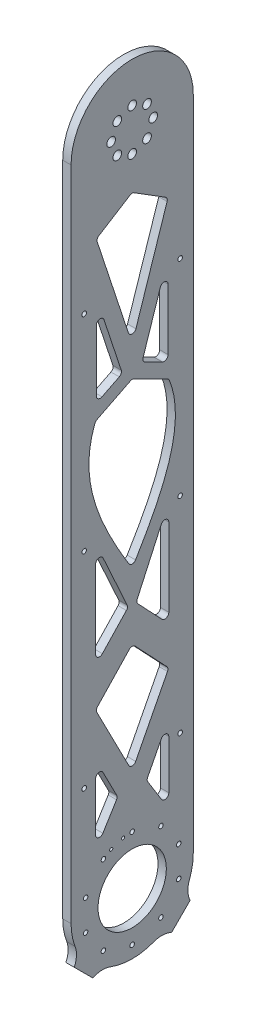
SolidWorks part; units mm, degrees
note: '?' marks a value the reader was unsure of.
material "6061 Alloy"
ref_plane "Front Plane" through (0, 0, 0) normal (0, 0, 1) x (1, 0, 0)
ref_plane "Top Plane" through (0, 0, 0) normal (0, 1, 0) x (1, 0, 0)
ref_plane "Right Plane" through (0, 0, 0) normal (1, 0, 0) x (0, 0, -1)
sketch "Sketch1" plane through (0, 0, 0) normal (1, 0, 0) x (0, -1, 0)
  line L0 (0, 0) -> (500, 0) construction
  line L1 (0, 46.5) -> (500, 46.5)
  line L2 (0, -46.5) -> (500, -46.5)
  arc A0 (0, 46.5) -> (0, -46.5) centre (0, 0) ccw
  arc A1 (500, -46.5) -> (500, 46.5) centre (500, 0) ccw
  circle A2 centre (0, 0) radius 16 construction
  circle A3 centre (-16, 0) radius 3.3
  circle A4 centre (-11.3137, 11.3137) radius 3.3
  circle A5 centre (0, 16) radius 3.3
  circle A6 centre (11.3137, 11.3137) radius 3.3
  circle A7 centre (16, 0) radius 3.3
  circle A8 centre (11.3137, -11.3137) radius 3.3
  circle A27 centre (500, 0) radius 37.25 construction
  circle A28 centre (537.25, 0) radius 1.7
  circle A29 centre (500, 0) radius 37.25 construction
  circle A30 centre (537.25, 0) radius 1.7
  circle A31 centre (530.1359, -21.895) radius 1.7
  circle A32 centre (511.5109, -35.4269) radius 1.7
  circle A33 centre (488.4891, -35.4269) radius 1.7
  circle A34 centre (469.8641, -21.895) radius 1.7
  circle A35 centre (462.75, 0) radius 1.7
  circle A36 centre (469.8641, 21.895) radius 1.7
  circle A37 centre (488.4891, 35.4269) radius 1.7
  circle A38 centre (511.5109, 35.4269) radius 1.7
  circle A39 centre (530.1359, 21.895) radius 1.7
  circle A40 centre (500, 0) radius 26
  circle A41 centre (0, -16) radius 3.3
  circle A42 centre (-11.3137, -11.3137) radius 3.3
  point P3 (250, 0)
  point P25 (0, 0)
  point P52 (500, 0)
  point P61 (500, 0)
  dimension "D3" = 32
  dimension "D4" = 6.6
  dimension "D2" = 74.5
  dimension "D7" = 3.4
  dimension "D8" = 3.4
  dimension "D10" = 52
  dimension "D6" = 46.5
  dimension "D1" = 500
  dimension "D5" = 8
  dimension "D9" = 10
extrude "Boss-Extrude1" add sketch "Sketch1" along normal blind 6.35 contours L2 A1 L1 A0 A40 A39 A38 A37 A36 A35 A34 A33 A32 A31 A28 A8 A7 A6 A5 A4 A3
ref_axis "Axis1" through (6.35, -500, 0) along (-1, 0, 0)?
sketch "Sketch3" plane through (6.35, 0, 0) normal (1, 0, 0) x (0, 0, -1)
  line L0 (0, -500) -> (0, 0) construction
  line L1 (0, -422.848) -> (27.8582, -368.6328)
  line L2 (0, -422.848) -> (-27.8582, -368.6328)
  line L3 (-27.8582, -368.6328) -> (0, -339.1393)
  line L4 (0, -339.1393) -> (27.8582, -368.6328)
  line L5 (0, -41.3687) -> (-27.3129, -58.4352)
  line L6 (-27.3129, -58.4352) -> (0, -141.249)
  line L7 (0, -141.249) -> (27.3129, -58.4352)
  line L8 (27.3129, -58.4352) -> (0, -41.3687)
  line L9 (3, -313.1891) -> (27.8582, -339.5065)
  line L10 (27.8582, -339.5065) -> (27.8582, -258.646)
  line L11 (27.8582, -258.646) -> (3, -313.1891)
  line L12 (-27.8582, -339.5065) -> (-27.8582, -258.646)
  line L13 (-3, -313.1891) -> (-27.8582, -339.5065)
  line L14 (-27.8582, -258.646) -> (-3, -313.1891)
  line L15 (-27.8582, -401.4529) -> (-11, -434.2608)
  line L16 (-11, -434.2608) -> (-27.8582, -461.4818)
  line L17 (-27.8582, -461.4818) -> (-27.8582, -401.4529)
  line L18 (11, -434.2608) -> (27.8582, -461.4818)
  line L19 (27.8582, -401.4529) -> (11, -434.2608)
  line L20 (27.8582, -461.4818) -> (27.8582, -401.4529)
  line L21 (0, -164.2489) -> (-27.8582, -178.2005)
  line L22 (0, -164.2489) -> (27.8582, -178.2005)
  line L23 (7.5, -156.821) -> (27.3129, -96.7475)
  line L24 (27.3129, -96.7475) -> (27.3129, -166.7434)
  line L25 (27.3129, -166.7434) -> (7.5, -156.821)
  line L26 (-27.3129, -96.7475) -> (-27.3129, -166.7434)
  line L27 (-7.5, -156.821) -> (-27.3129, -96.7475)
  line L28 (-27.3129, -166.7434) -> (-7.5, -156.821)
  spline S0 degree 3 poles (-27.8582, -178.2005) (-43.7791, -216.0933) (-18.6166, -258.2761) (0, -289.085) knots 0 0 0 0 1 1 1 1
  spline S1 degree 3 poles (27.8582, -178.2005) (43.7791, -216.0933) (18.6166, -258.2761) (0, -289.085) knots 0 0 0 0 1 1 1 1
  dimension "D1" = 15
  dimension "D2" = 20
  dimension "D3" = 12
  dimension "D4" = 10
  dimension "D5" = 6
  dimension "D6" = 15
  dimension "D7" = 22
extrude "Cut-Extrude1" cut sketch "Sketch3" against normal through all
fillet "Fillet1" radius 3 30 edges at (3.175, -58.4352, -27.3129) (3.175, -41.3687, 0) (3.175, -58.4352, 27.3129) (3.175, -141.249, 0) (3.175, -289.085, 0) (3.175, -164.2489, 0) (3.175, -401.4529, 27.8582) (3.175, -434.2608, 11) (3.175, -461.4818, 27.8582) (3.175, -461.4818, -27.8582) (3.175, -434.2608, -11) (3.175, -401.4529, -27.8582) (3.175, -368.6328, -27.8582) (3.175, -339.1393, 0) (3.175, -368.6328, 27.8582) (3.175, -422.848, 0) (3.175, -313.1891, 3) (3.175, -339.5065, 27.8582) (3.175, -258.646, 27.8582) (3.175, -178.2005, -27.8582) (3.175, -178.2005, 27.8582) (3.175, -339.5065, -27.8582) (3.175, -313.1891, -3) (3.175, -258.646, -27.8582) (3.175, -96.7475, 27.3129) (3.175, -166.7434, 27.3129) (3.175, -156.821, 7.5) (3.175, -166.7434, -27.3129) (3.175, -156.821, -7.5) (3.175, -96.7475, -27.3129)
sketch "Sketch4" plane through (6.35, 0, 0) normal (1, 0, 0) x (0, 0, -1)
  line L0 (0, 46.5) -> (-113.1579, 46.5) construction
  line L1 (-46.5, 0) -> (-46.5, -500) construction
  line L2 (-46.5, -100) -> (46.5, -100) construction
  line L3 (46.5, 0) -> (46.5, -500) construction
  line L4 (-46.5, -106.35) -> (46.5, -106.35) construction
  line L5 (-36.5, -100) -> (-36.5, -106.35) construction
  line L6 (0, 0) -> (0, -106.35) construction
  line L7 (0, -106.35) -> (0, -256.35) construction
  line L8 (0, -256.35) -> (46.5, -256.35) construction
  line L9 (46.5, -262.7) -> (-46.5, -262.7) construction
  line L10 (0, -181.35) -> (46.5, -181.35) construction
  line L11 (0, -262.7) -> (0, -412.7) construction
  line L12 (0, -412.7) -> (46.5, -412.7) construction
  line L13 (0, -337.7) -> (46.5, -337.7) construction
  arc A1 (46.5, 0) -> (-46.5, 0) centre (0, 0) ccw construction
  circle A2 centre (-36.5, -103.175) radius 1.75
  circle A3 centre (36.5, -103.175) radius 1.75
  circle A4 centre (-36.5, -259.525) radius 1.75
  circle A5 centre (36.5, -259.525) radius 1.75
  circle A6 centre (-36.5, -415.875) radius 1.75
  circle A7 centre (36.5, -415.875) radius 1.75
  point P17 (-36.5, -103.175)
  dimension "D1" = 3.5
  dimension "D2" = 6.35
  dimension "D3" = 10
  dimension "D4" = 146.5
  dimension "D5" = 150
  dimension "D6" = 6.35
  dimension "D7" = 81.35
  dimension "D8" = 150
  dimension "D9" = 81.35
extrude "Cut-Extrude2" cut sketch "Sketch4" against normal through all
sketch "Sketch5" plane through (6.35, 0, 0) normal (1, 0, 0) x (0, 0, -1)
  line L0 (-6.9161, -463.3431) -> (-15.9511, -466.2787) construction
  line L1 (-7.2252, -475.0096) -> (7.4545, -470.2399) construction
  line L2 (-21.895, -469.8641) -> (0, -462.75) construction
  line L3 (-10.9475, -466.3071) -> (0, -500) construction
  circle A0 centre (-6.9161, -463.3431) radius 1.2
  circle A1 centre (-15.9511, -466.2787) radius 1.2
  circle A2 centre (0, -500) radius 26 construction
  circle A3 centre (0, -500) radius 26 construction
  circle A4 centre (0, -462.75) radius 1.7 construction
  circle A5 centre (-21.895, -469.8641) radius 1.7 construction
  circle A6 centre (0, -462.75) radius 1.7 construction
  circle A7 centre (-21.895, -469.8641) radius 1.7 construction
  point P16 (-11.4336, -464.8109)
  dimension "D1" = 2.4
  dimension "D2" = 9.5
  dimension "D3" = 11
extrude "Cut-Extrude4" cut sketch "Sketch5" against normal through all
sketch "Sketch6" plane through (6.35, 0, 0) normal (1, 0, 0) x (0, 0, -1)
  line L2 (-23.6842, -540.0163) -> (-29.9682, -544.1104) construction
  line L3 (-44.1104, -529.9682) -> (-29.9682, -544.1104)
  line L4 (0, -500) -> (0, -546.5) construction
  line L5 (-37.0393, -537.0393) -> (0, -500) construction
  line L6 (-44.1104, -529.9682) -> (-40.0163, -523.6842) construction
  arc A0 (-46.5, -500) -> (46.5, -500) centre (0, -500) ccw construction
  arc A1 (-29.9682, -544.1104) -> (-16.4747, -543.4837) centre (-22.4977, -559.381) cw
  arc A4 (-44.1104, -529.9682) -> (-43.4837, -516.4747) centre (-59.381, -522.4977) ccw
  arc A5 (-16.4747, -543.4837) -> (-43.4837, -516.4747) centre (0, -500) cw
  dimension "D2" = 17
  dimension "D4" = 17
  dimension "D1" = 20
  dimension "D3" = 8
  dimension "D5" = 8
  dimension "D6" = 7.5
  dimension "D7" = 45
  dimension "D8" = 7.5
extrude "Boss-Extrude2" add sketch "Sketch6" against normal up to surface (6.35 mm away) up to face at (0, -463.3431, 5.7161)
sketch "Sketch7" plane through (0, -287.0393, 287.0393) normal (0, -0.7071, 0.7071) x (1, 0, 0)
  line L0 (0, -343.5534) -> (6.35, -343.5534) construction
  line L1 (0, -363.5534) -> (6.35, -363.5534) construction
  line L2 (0, -363.5534) -> (0, -343.5534) construction
  point P0 (3.175, -347.5534)
  point P1 (3.175, -360.5841)
  dimension "D1" = 4
  dimension "D2" = 2.9693
  dimension "D3" = 3.175
hole_wizard "Tap Drill for M3x0.5 Tap1" positions "Sketch7" profile "Sketch8" hole size "M3x0.5" standard "ANSI Metric"
sketch "Sketch8" plane through (3.175, -532.7967, 41.282) normal (1, 0, 0) x (0, -0.7071, -0.7071)
  line L0 (0, 0) -> (0, 5.7511)
  line L1 (0, 5.7511) -> (1.25, 5)
  line L2 (1.25, 5) -> (1.25, 0)
  line L5 (1.25, 0) -> (0, 0)
  line L10 (0, 5.7511) -> (-1.25, 5) construction
  line L11 (0, -6.35) -> (0, 107.95) construction
  dimension "Hole Dia." = 2.5
  dimension "Hole Depth" = 5
  dimension "Drill Angle" = 118
pattern_circular "CirPattern1" count 2 every 90 about axis through (0, -500, 0) along (1, 0, 0) of "Boss-Extrude2", "Tap Drill for M3x0.5 Tap1"
equation "\"L1L\"=500"
equation "\"D1@Sketch1\"=\"L1L\""
equation "\"L1Thick\"=6.35"
equation "\"D1@Boss-Extrude1\"=\"L1Thick\""
equation "\"Harm-Drive-Outer\"=74.5"
equation "\"D2@Sketch1\"=\"Harm-Drive-Outer\""
